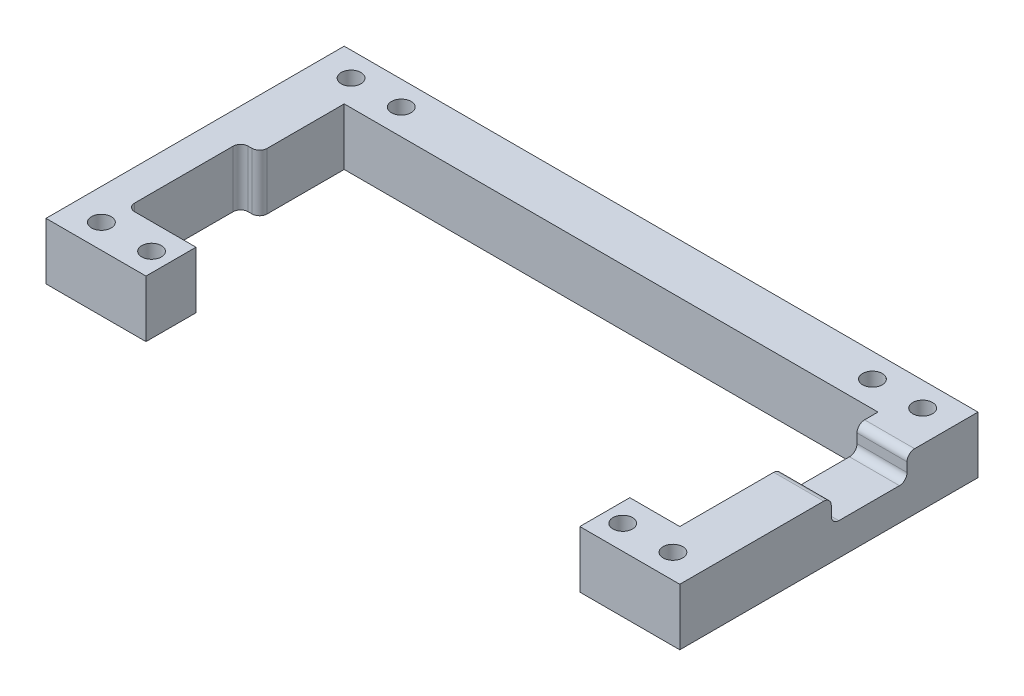
SolidWorks part; units mm, degrees
ref_plane "Front Plane" through (0, 0, 0) normal (0, 0, 1) x (1, 0, 0)
ref_plane "Top Plane" through (0, 0, 0) normal (0, 1, 0) x (1, 0, 0)
ref_plane "Right Plane" through (0, 0, 0) normal (1, 0, 0) x (0, 0, -1)
sketch "Sketch1" plane through (0, 0, 0) normal (0, 1, 0) x (1, 0, 0)
  line L0 (181.4198, 36.9979) -> (75.1552, 36.9979) construction
  line L1 (75.1552, 11.9979) -> (83.5372, 11.9979)
  line L2 (75.1552, 11.9979) -> (75.1552, 61.9979)
  line L3 (75.1552, 61.9979) -> (83.5372, 61.9979)
  line L4 (83.5372, 11.9979) -> (83.5372, 61.9979)
  line L5 (83.5372, 61.9979) -> (91.9192, 61.9979)
  line L6 (83.5372, 61.9979) -> (83.5372, 53.6159)
  line L7 (83.5372, 53.6159) -> (91.9192, 53.6159)
  line L8 (167.7876, 16.0648) -> (186.7138, 16.0648) construction
  line L9 (83.5372, 11.9979) -> (91.9192, 11.9979)
  line L10 (83.5372, 11.9979) -> (83.5372, 20.3799)
  line L11 (83.5372, 20.3799) -> (91.9192, 20.3799)
  line L12 (91.9192, 11.9979) -> (91.9192, 20.3799)
  line L13 (75.1552, 61.9979) -> (181.4198, 61.9979)
  line L17 (181.4198, 61.9979) -> (173.0378, 61.9979)
  line L18 (181.4198, 61.9979) -> (181.4198, 11.9979)
  line L19 (181.4198, 11.9979) -> (173.0378, 11.9979)
  line L20 (173.0378, 61.9979) -> (173.0378, 11.9979)
  line L21 (173.0378, 61.9979) -> (164.6558, 61.9979)
  line L22 (173.0378, 61.9979) -> (173.0378, 53.6159)
  line L23 (173.0378, 53.6159) -> (164.6558, 53.6159)
  line L25 (173.0378, 11.9979) -> (164.6558, 11.9979)
  line L26 (173.0378, 11.9979) -> (173.0378, 20.3799)
  line L27 (173.0378, 20.3799) -> (164.6558, 20.3799)
  line L28 (164.6558, 11.9979) -> (164.6558, 20.3799)
  line L29 (128.2875, 61.9979) -> (128.2875, -9.1774) construction
  line L30 (164.6558, 53.6159) -> (91.9192, 53.6159)
  circle A0 centre (167.7876, 57.931) radius 1.651
  circle A1 centre (167.7876, 16.0648) radius 1.651
  circle A2 centre (88.7875, 16.0648) radius 1.651
  circle A3 centre (88.7875, 57.931) radius 1.651
  circle A4 centre (176.2028, 16.0648) radius 1.651
  circle A5 centre (80.3722, 16.0648) radius 1.651
  circle A6 centre (80.3722, 57.931) radius 1.651
  circle A7 centre (176.2028, 57.931) radius 1.651
  point P32 (91.9192, 16.1889)
  point P34 (88.7875, 57.931)
  point P35 (88.7875, 16.0648)
  dimension "D15" = 3.302
  dimension "D16" = 3.1342
  dimension "D6" = 79.0001
  dimension "D18" = 3.302
  dimension "D2" = 47.9153
  dimension "D1" = 8.382
  dimension "D3" = 50
  dimension "D4" = 8.382
  dimension "D5" = 50
  dimension "D7" = 8.382
  dimension "D8" = 8.382
  dimension "D9" = 8.382
  dimension "D10" = 8.382
  dimension "D11" = 8.382
  dimension "D12" = 8.382
  dimension "D13" = 8.382
  dimension "D14" = 8.382
  dimension "D17" = 3.1317
extrude "Boss-Extrude1" add sketch "Sketch1" along normal blind 9.525 contours L1 L4 L3 L2 | L13 L3 L5 | L13 L20 L19 L18 | L13 L23 L20 | L28 L25 L20 L27 | L9 L12 L11 L4 | L5 L4 L7 | L1 L4 L2 | L20 L19 L18 region at (79.3025, 0, -36.9979) region at (83.6557, 0, -16.1889) region at (128.2875, 0, -57.804) region at (177.2725, 0, -36.9979) region at (172.9193, 0, -16.1889)
sketch "Sketch2" plane through (181.4198, 0, 0) normal (1, 0, 0) x (0, 0, -1)
  line L0 (61.9979, 9.525) -> (11.9979, 9.525) construction
  line L1 (37.3979, 9.525) -> (50.0979, 9.525)
  line L2 (37.3979, 9.525) -> (37.3979, 5.4254)
  line L3 (37.3979, 5.4254) -> (50.0979, 5.4254)
  line L4 (50.0979, 9.525) -> (50.0979, 5.4254)
  line L5 (11.9979, 9.525) -> (11.9979, 0) construction
  dimension "D1" = 25.4
  dimension "D2" = 12.7
extrude "Cut-Extrude7" cut sketch "Sketch2" against normal blind 8.89 contours L2 L3 L4 L1
fillet "Fillet2" radius 1.27 4 edges at (177.2288, 5.4254, -37.3979) (177.2288, 9.525, -37.3979) (177.2288, 9.525, -50.0979) (177.2288, 5.4254, -50.0979)
sketch "Sketch4" plane through (0, 9.525, 0) normal (0, 1, 0) x (1, 0, 0)
  line L1 (83.5372, 20.3799) -> (80.3622, 20.3799)
  line L2 (83.5372, 20.3799) -> (83.5372, 39.4299)
  line L3 (83.5372, 39.4299) -> (80.3622, 39.4299)
  line L4 (80.3622, 20.3799) -> (80.3622, 39.4299)
  dimension "D1" = 3.175
  dimension "D2" = 19.05
extrude "Cut-Extrude8" cut sketch "Sketch4" against normal through all
fillet "Fillet3" radius 1.27 3 edges at (80.3622, 4.7625, -20.3799) (80.3622, 4.7625, -39.4299) (83.5372, 4.7625, -39.4299)
